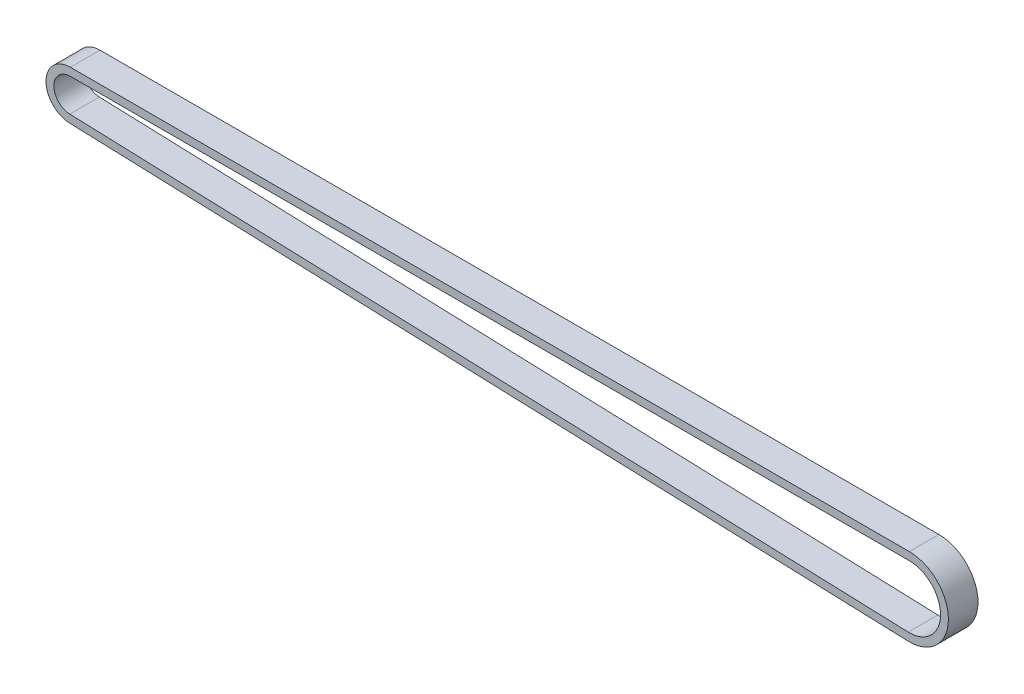
SolidWorks part; units mm, degrees
ref_plane "Front Plane" through (0, 0, 0) normal (0, 0, 1) x (1, 0, 0)
ref_plane "Top Plane" through (0, 0, 0) normal (0, 1, 0) x (1, 0, 0)
ref_plane "Right Plane" through (0, 0, 0) normal (1, 0, 0) x (0, 0, -1)
sketch "Sketch1" plane through (0, 0, 0) normal (0, 0, 1) x (1, 0, 0)
  line L0 (0, 7.8486) -> (269.9587, 7.8486)
  line L1 (0, 0) -> (269.9587, -4.7244) construction
  line L2 (-0.2746, -7.8438) -> (269.5187, -17.2897)
  line L3 (0, 5.3086) -> (269.9587, 5.3086)
  line L4 (-0.1857, -5.3053) -> (269.6076, -14.7513)
  arc A0 (0, 7.8486) -> (-0.2746, -7.8438) centre (0, 0) ccw
  arc A1 (269.5187, -17.2897) -> (269.9587, 7.8486) centre (269.9587, -4.7244) ccw
  arc A2 (269.6076, -14.7513) -> (269.9587, 5.3086) centre (269.9587, -4.7244) ccw
  arc A3 (0, 5.3086) -> (-0.1857, -5.3053) centre (0, 0) ccw
  dimension "D2" = 15.6972
  dimension "D3" = 25.146
  dimension "D1" = 270
  dimension "D4" = 2.54
extrude "Boss-Extrude1" add sketch "Sketch1" along normal blind 9.525
